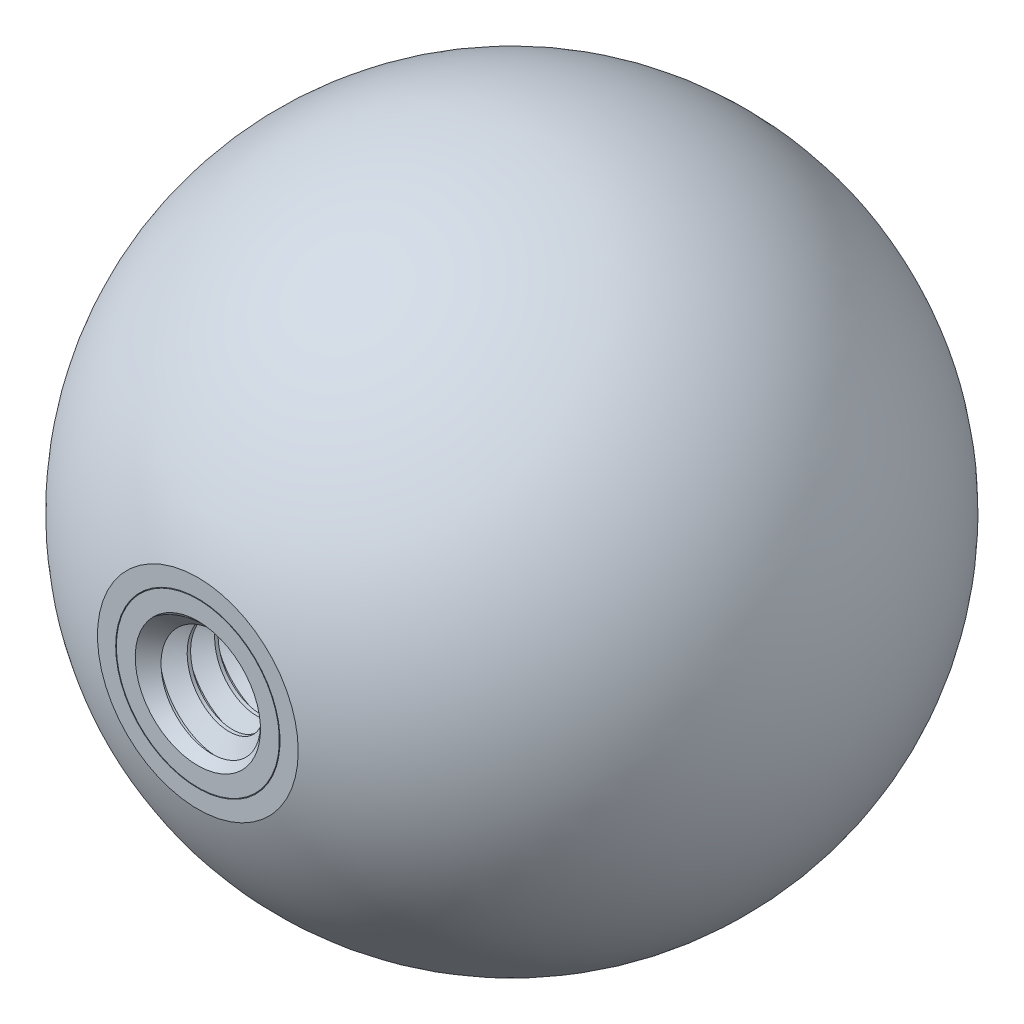
SolidWorks part; units mm, degrees
ref_plane "Front Plane" through (0, 0, 0) normal (0, 0, 1) x (1, 0, 0)
ref_plane "Top Plane" through (0, 0, 0) normal (0, 1, 0) x (1, 0, 0)
ref_plane "Right Plane" through (0, 0, 0) normal (1, 0, 0) x (0, 0, -1)
sketch "Sketch1" plane through (0, 0, 0) normal (1, 0, 0) x (0, 0, -1)
  line L0 (-12.7, 0) -> (12.7, 0) construction
  line L3 (-12.0968, 2.413) -> (-2.5717, 2.413)
  line L4 (-2.5717, 2.413) -> (-2.5717, 0)
  line L5 (-12.0968, 2.413) -> (-12.0968, 3.8676)
  arc A0 (12.7, 0) -> (-12.0968, 3.8676) centre (0, 0) ccw
  arc A1 (-12.0968, 3.8676) -> (-12.7, 0) centre (0, 0) ccw construction
  point P3 (-12.0968, 0)
  point P4 (0, 0)
  dimension "D1" = 0.6032
sketch "Sketch2" plane through (0, 0, 0) normal (1, 0, 0) x (0, 0, -1)
  line L0 (-12.0968, 2.413) -> (-12.0968, 3.8676) construction
  line L1 (-12.0968, 2.413) -> (-2.5717, 2.413) construction
  line L5 (-2.5717, 2.413) -> (-2.5717, 0) construction
  line L7 (-2.5717, 2.413) -> (-2.5717, 0)
  line L9 (-2.5717, 0) -> (12.7, 0)
  line L10 (-12.0968, 2.413) -> (-12.0968, 3.8676)
  line L11 (-12.0968, 2.413) -> (-2.5717, 2.413)
  arc A0 (12.7, 0) -> (-12.0968, 3.8676) centre (0, 0) ccw construction
  arc A4 (12.7, 0) -> (-12.0968, 3.8676) centre (0, 0) ccw
revolve "Revolve1" add sketch "Sketch2" angle 360 about L0
sketch "Sketch6" plane through (0, 0, 12.0968) normal (0, 0, -1) x (-1, 0, 0)
  line L0 (0, 2.413) -> (0, 3.8676) construction
  circle A0 centre (0, 0) radius 3.1403
  point P4 (0, 3.1403)
extrude "Cut-Extrude-Thin1" cut sketch "Sketch6" along normal up to surface (9.525 mm away) thin up to face at (2.413, 0, 2.5717) thin type one direction wall 0.0254
sketch "Sketch10" plane through (0, 0, 0) normal (0, 0, 1) x (1, 0, 0)
  line L0 (0, 0) -> (1.7062, -1.7062) construction
  line L1 (0, 2.413) -> (0, 0) construction
  point P6 (1.7062, -1.7062)
  dimension "D1" = 45
sketch "Sketch9" plane through (0, 0, 0) normal (1, 0, 0) x (0, 0, -1)
  line L0 (-12.0968, 2.413) -> (-2.5717, 2.413)
  line L1 (-2.5717, 2.413) -> (-2.5717, 0)
  line L2 (-2.5717, 0) -> (-2.5717, -2.413)
  line L3 (-2.5717, -2.413) -> (-12.0968, -2.413)
ref_axis "Center Axis 1" through (0, 0, -20.9173) along (0, 0, 1)
ref_plane "Contact Plane 1" through (0, 0, 2.5717) normal (0, 0, -1) x (-1, 0, 0)
sketch "Sketch3" plane through (0, 0, 12.0968) normal (0, 0, -1) x (-1, 0, 0)
  circle A0 centre (0, 0) radius 2.413
sketch "Sketch7" plane through (0, 0, 12.0968) normal (0, 0, 1) x (1, 0, 0)
  circle A0 centre (0, 0) radius 2.413 construction
  circle A1 centre (0, 0) radius 2.413
extrude "Boss-Extrude1" add sketch "Sketch7" against normal up to surface (9.525 mm away) separate body up to face at (2.413, 0, 2.5717)
sketch "Sketch8" plane through (0, 0, 12.0968) normal (0, 0, 1) x (1, 0, 0)
  circle A0 centre (0, 0) radius 2.413 construction
  circle A1 centre (0, 0) radius 2.413
extrude "Boss-Extrude2" add sketch "Sketch8" against normal up to surface (9.525 mm away) up to face at (2.413, 0, 2.5717)
curve "Helix/Spiral1" pitch 1.0583 height 10.5833 radius 2.413 centre (0, 0, 12.0968) axis (0, 0, -1) start towards (0, 1, 0) parameters "Thread Pitch"=1.0583
sketch "Sketch4" plane through (0, 0, 0) normal (1, 0, 0) x (0, 0, -1)
  line L0 (-13.0228, 2.413) -> (-12.0968, 2.413)
  line L1 (-12.0968, 2.413) -> (-12.4936, 1.7256)
  line L2 (-12.4936, 1.7256) -> (-12.6259, 1.7256)
  line L3 (-12.6259, 1.7256) -> (-13.0228, 2.413)
  line L4 (-12.5598, 2.413) -> (-12.5598, 1.7256) construction
  line L5 (-12.8244, 2.0693) -> (-12.2952, 2.0693) construction
  dimension "D1" = 0.1323
  dimension "D2" = 0.5292
  dimension "D3" = 60
sweep "Cut-Sweep1" cut profiles "Sketch4" path "Helix/Spiral1" align with end faces yes
combine bodies "Combine1" operation type subtract main body 109 bodies to subtract 111
sketch "Sketch5" plane through (0, 0, 12.0968) normal (0, 0, 1) x (1, 0, 0)
  circle A0 centre (0, 0) radius 2.413
extrude "Cut-Extrude1" cut sketch "Sketch5" along normal through all and the other way through all draft 45
equation "\"D3@Helix/Spiral1\"=\"Thread Length@Sketch1\"+\"Thread Pitch@Helix/Spiral1\""
equation "\"D1@Sketch4\"=\"Thread Pitch@Helix/Spiral1\"*.125"
equation "\"D2@Sketch4\"=\"Thread Pitch@Helix/Spiral1\"*.5"
equation "\"D1@Sketch1\" = \"Thread Dia@Sketch1\" * .125"
